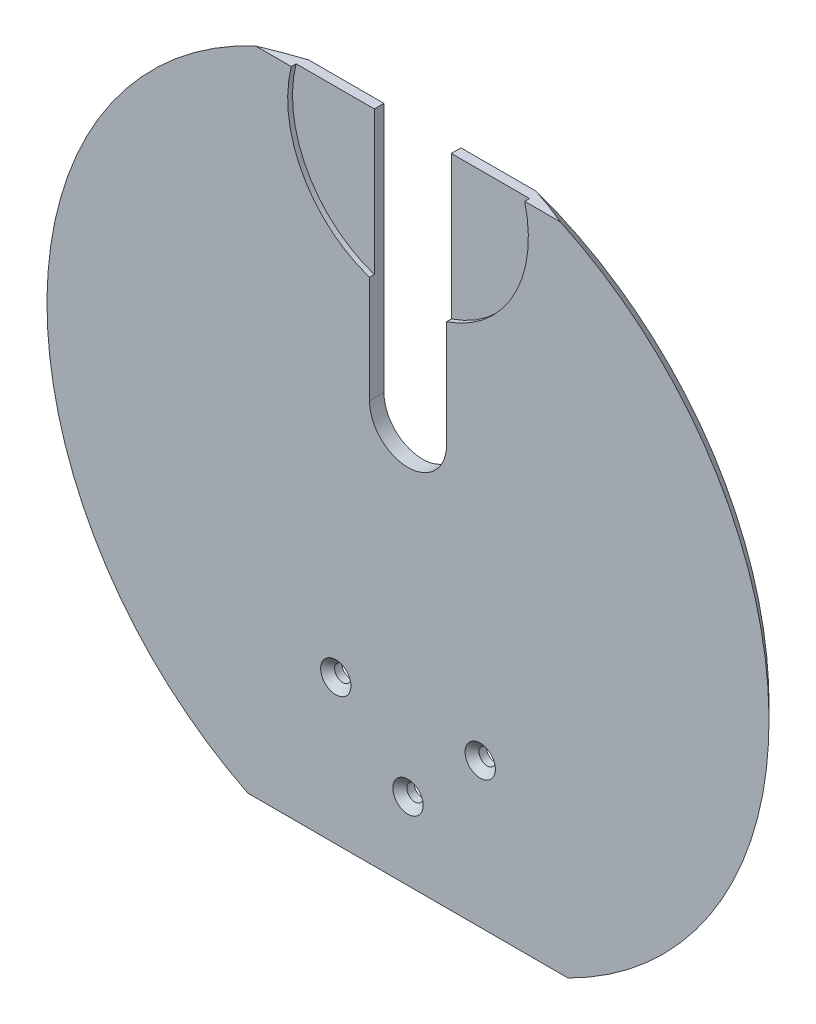
SolidWorks part; units mm, degrees
material "PET"
ref_plane "Front Plane" through (0, 0, 0) normal (0, 0, 1) x (1, 0, 0)
ref_plane "Top Plane" through (0, 0, 0) normal (0, 1, 0) x (1, 0, 0)
ref_plane "Right Plane" through (0, 0, 0) normal (1, 0, 0) x (0, 0, -1)
sketch "Sketch1" plane through (0, 0, 0) normal (0, 0, 1) x (1, 0, 0)
  line L1 (-33.2265, -67.2384) -> (-33.2265, -65) construction
  line L2 (-33.2265, -67.2384) -> (33.2265, -67.2384)
  line L4 (-31.6386, 68) -> (31.6386, 68)
  line L5 (-33.2265, -65) -> (33.2265, -65) construction
  line L6 (82.5, 0) -> (-82.5, 0) construction
  arc A4 (33.2265, -65) -> (26.5518, 68) centre (0, 0) ccw construction
  arc A6 (-31.6386, 68) -> (-33.2265, -67.2384) centre (0, 0) ccw
  arc A7 (-26.5518, 68) -> (-33.2265, -65) centre (0, 0) ccw construction
  arc A8 (33.2265, -67.2384) -> (31.6386, 68) centre (0, 0) ccw
  dimension "D2" = 150
  dimension "D3" = 146
  dimension "D9" = 68
  dimension "D11" = 65
extrude "Boss-Extrude2" add sketch "Sketch1" along normal blind 3
sketch "Sketch2" plane through (0, 0, 3) normal (0, 0, 1) x (1, 0, 0)
  line L0 (0, -2.2) -> (0, 2.2) construction
  line L2 (-33.2265, -67.2384) -> (33.2265, -67.2384) construction
  point P3 (-15, -37.2384)
  point P6 (0, -51.2384)
  point P13 (15, -37.2384)
  dimension "D1" = 30
  dimension "D2" = 14
  dimension "D3" = 16
hole_wizard "CSK for M3 Countersunk Flat Head Screw1" positions "Sketch2" profile "Sketch3" countersink size "M3" standard "ISO" end condition up to next
sketch "Sketch3" plane through (-15, -37.2384, 3) normal (1, 0, 0) x (0, -1, 0)
  line L0 (0, 0) -> (0, 3)
  line L1 (0, 3) -> (1.7, 3)
  line L2 (1.7, 3) -> (1.7, 1.45)
  line L3 (1.7, 1.45) -> (3.15, 0)
  line L5 (3.15, 0) -> (0, 0)
  line L6 (-1.7, 1.45) -> (-3.15, 0) construction
  line L11 (0, -6.35) -> (0, 107.95) construction
  dimension "Thru Hole Dia." = 3.4
  dimension "Thru Hole Depth" = 3
  dimension "Near C'Sink Dia." = 6.3
  dimension "Near C'Sink Angle" = 90
sketch "Sketch4" plane through (0, 0, 3) normal (0, 0, 1) x (1, 0, 0)
  line L0 (0, -2.2) -> (0, 2.2) construction
  line L8 (-8, 16) -> (-8, 68)
  line L9 (-8, 68) -> (8, 68)
  line L10 (8, 16) -> (8, 68)
  line L12 (31.6386, 68) -> (-31.6386, 68) construction
  arc A0 (-8, 16) -> (8, 16) centre (0, 16) ccw
  point P3 (0, 8)
  dimension "D1" = 8
  dimension "D2" = 60
extrude "Cut-Extrude1" cut sketch "Sketch4" against normal up to next contours L8 A0 L10 region at (0, 38.8311, 3)
sketch "Sketch5" plane through (0, 0, 3) normal (0, 0, 1) x (1, 0, 0)
  circle A0 centre (0, 61.9) radius 25
  dimension "D1" = 50
  dimension "D2" = 61.9
extrude "Cut-Extrude2" cut sketch "Sketch5" against normal blind 1
chamfer "Chamfer3" distance 3 2 edges at (-74.9948, 0.8806, 0) (74.9948, 0.8806, 0) tangent propagation no
sketch "Sketch6" plane through (0, 0, 0) normal (0, 0, 1) x (1, 0, 0)
  line L0 (-33.2265, -67.2384) -> (-33.2265, 68)
  line L1 (-33.2265, 68) -> (33.2265, 68)
  line L2 (33.2265, 68) -> (33.2265, -67.2384)
  line L3 (33.2265, -67.2384) -> (-33.2265, -67.2384)
  line L4 (31.6386, 68) -> (24.2444, 68) construction
  line L5 (-33.2265, -67.2384) -> (33.2265, -67.2384) construction
  point P2 (-33.2265, -67.2384)
extrude "Cut-Extrude3" [suppressed] cut sketch "Sketch6" along normal through all flip side to cut
